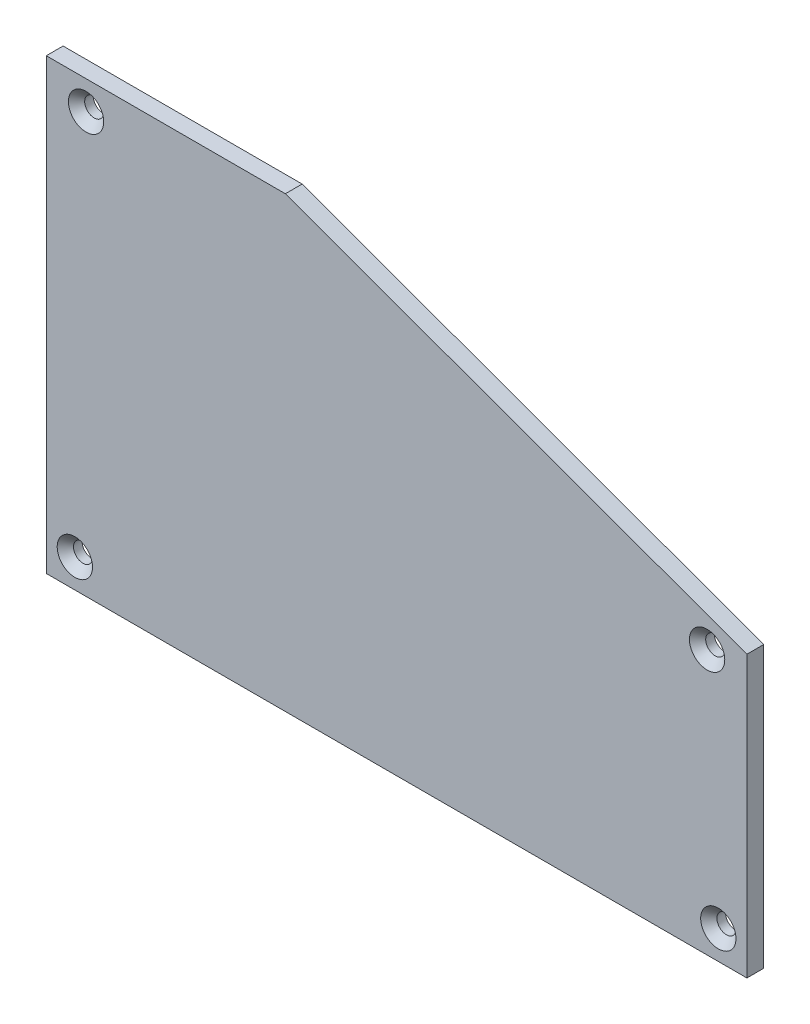
SolidWorks part; units mm, degrees
ref_plane "Спереди" through (0, 0, 0) normal (0, 0, 1) x (1, 0, 0)
ref_plane "Сверху" through (0, 0, 0) normal (0, 1, 0) x (1, 0, 0)
ref_plane "Справа" through (0, 0, 0) normal (1, 0, 0) x (0, 0, -1)
sketch "Эскиз1" plane through (0, 0, 0) normal (0, 0, 1) x (1, 0, 0)
  line L0 (-53.75, 74) -> (-11.0949, 74) construction
  line L1 (-11.0949, 74) -> (71.25, 44.0289) construction
  line L2 (71.25, 41.9283) -> (71.25, -6) construction
  line L3 (71.25, -6) -> (-53.75, -6) construction
  line L4 (-53.75, -6) -> (-53.75, 71) construction
  line L5 (-53.75, 74) -> (-11.0949, 74)
  line L6 (-11.0949, 74) -> (71.25, 44.0289)
  line L7 (71.25, 44.0289) -> (71.25, -6)
  line L8 (71.25, -6) -> (-53.75, -6)
  line L9 (-53.75, -6) -> (-53.75, 74)
extrude "Бобышка-Вытянуть1" add sketch "Эскиз1" along normal blind 3
hole_wizard "Зенковка для винта с потайной головкой M31" positions "Эскиз4" profile "Эскиз5" countersink size "M3" standard "DIN" end condition through all
sketch "Эскиз4" plane through (0, 0, 3) normal (0, 0, 1) x (1, 0, 0)
  point P0 (-46.65, 68.9)
  point P3 (-48.65, -0.9)
  point P7 (64.15, 41.1858)
  point P10 (66.15, -0.9)
sketch "Эскиз5" plane through (-46.65, 68.9, 3) normal (1, 0, 0) x (0, -1, 0)
  line L0 (0, 0) -> (0, 3)
  line L1 (0, 3) -> (1.7, 3)
  line L2 (1.7, 3) -> (1.7, 1.45)
  line L3 (1.7, 1.45) -> (3.15, 0)
  line L5 (3.15, 0) -> (0, 0)
  line L6 (-1.7, 1.45) -> (-3.15, 0) construction
  line L11 (0, -6.35) -> (0, 107.95) construction
  dimension "Диаметр сквозного отверстия" = 3.4
  dimension "Глубина сквозного отверстия" = 3
  dimension "Диаметр передней зенковки" = 6.3
  dimension "Угол передней зенковки" = 90
